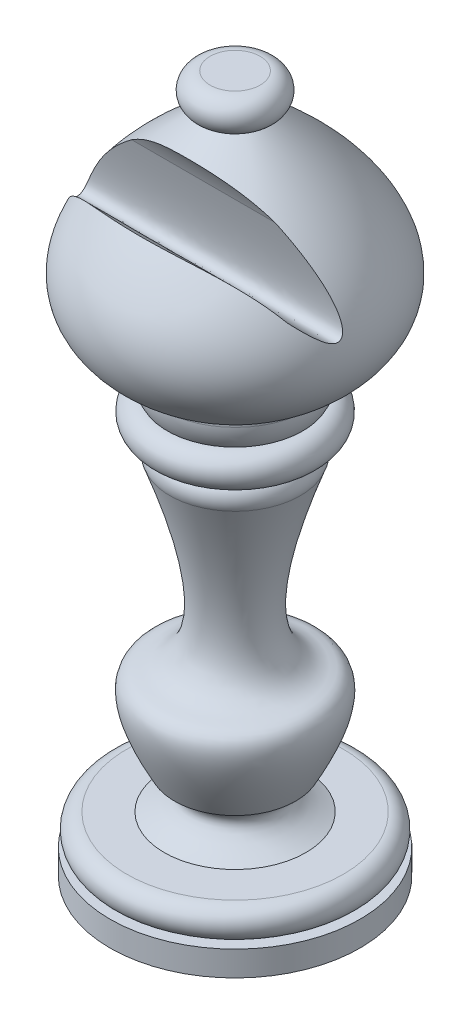
SolidWorks part; units mm, degrees
ref_plane "Front Plane" through (0, 0, 0) normal (0, 0, 1) x (1, 0, 0)
ref_plane "Top Plane" through (0, 0, 0) normal (0, 1, 0) x (1, 0, 0)
ref_plane "Right Plane" through (0, 0, 0) normal (1, 0, 0) x (0, 0, -1)
sketch "Sketch1" plane through (0, 0, 0) normal (0, 1, 0) x (1, 0, 0)
  line L1 (-16.1768, -16.5151) -> (16.1768, -16.5151) construction
  line L2 (-16.1768, -16.5151) -> (-16.1768, 16.5151) construction
  line L3 (-16.1768, 16.5151) -> (16.1768, 16.5151) construction
  line L4 (16.1768, -16.5151) -> (16.1768, 16.5151) construction
  line L5 (-16.1768, -16.5151) -> (16.1768, 16.5151) construction
  line L6 (-16.1768, 16.5151) -> (16.1768, -16.5151) construction
  circle A0 centre (0, 0) radius 15
  point P0 (0, 0)
  dimension "D1" = 30
extrude "Boss-Extrude1" add sketch "Sketch1" along normal blind 3
sketch "Sketch2" plane through (0, 0, 0) normal (0, 0, 1) x (1, 0, 0)
  line L0 (0, 0) -> (0, 11.4072) construction
  line L1 (15, 3) -> (-15, 3) construction
  line L2 (13, 3) -> (0, 3)
  line L3 (13, 6.6728) -> (8.4994, 6.6728)
  line L5 (7.2741, 11.4072) -> (0, 11.4072)
  line L6 (0, 3) -> (0, 11.4072)
  arc A0 (13, 3) -> (13, 6.6728) centre (13, 4.8364) ccw
  spline S0 degree 2 poles (8.4994, 6.6728) (2.7826, 9.1026) (7.2741, 11.4072) knots 0 0 0 1 1 1
  dimension "D1" = 2
revolve "Revolve1" add sketch "Sketch2" angle 360 about L0
sketch "Sketch3" plane through (0, 0, 0) normal (0, 0, 1) x (1, 0, 0)
  line L0 (0, 0) -> (0, 53.285) construction
  line L2 (7.2741, 11.4072) -> (-7.2741, 11.4072) construction
  line L3 (7.2741, 11.4072) -> (0, 11.4072)
  line L4 (6.0335, 46.296) -> (8.1263, 46.296)
  line L5 (8.1263, 50.296) -> (8.8239, 50.296)
  line L6 (8.8239, 50.296) -> (8.8239, 53.285)
  line L7 (8.8239, 53.285) -> (0, 53.285)
  line L8 (0, 11.4072) -> (0, 53.285)
  arc A0 (7.8298, 43.4168) -> (6.0335, 46.296) centre (6.0335, 44.296) ccw
  arc A1 (8.1263, 46.296) -> (8.1263, 50.296) centre (8.1263, 48.296) ccw
  spline S0 degree 2 poles (7.8298, 43.4168) (0.4858, 23.2013) (12.4322, 20.9438) (7.2741, 11.4072) knots 0 0 0 0.660085 1 1 1
  dimension "D1" = 2
revolve "Revolve2" add sketch "Sketch3" angle 360 about L0
sketch "Sketch4" plane through (0, 0, 0) normal (1, 0, 0) x (0, 0, -1)
  line L0 (0, 53.285) -> (0, 81.5387) construction
  line L1 (8.8239, 53.285) -> (-8.8239, 53.285) construction
  line L2 (0, 53.285) -> (8.8239, 53.285)
  line L3 (0, 53.285) -> (0, 81.5387)
  spline S0 degree 2 poles (0, 81.5387) (26.7597, 63.2839) (8.8239, 53.285) knots 0 0 0 1 1 1
revolve "Revolve3" add sketch "Sketch4" angle 360 about L3
sketch "Sketch5" plane through (0, 0, 0) normal (1, 0, 0) x (0, 0, -1)
  line L0 (-19.9005, 74.7415) -> (-13.287, 82.3198)
  spline S0 degree 2 poles (-19.9005, 74.7415) (-11.6755, 74.63) (-6.805, 67.3863) knots 0 0 0 1 1 1
  spline S1 degree 2 poles (-6.805, 67.3863) (0.2222, 59.7056) (-3.8076, 74.0978) knots 0 0 0 1 1 1
  spline S2 degree 2 poles (-13.287, 82.3198) (-6.4144, 80.3398) (-3.8076, 74.0978) knots 0 0 0 1 1 1
extrude "Cut-Extrude1" cut sketch "Sketch5" against normal through all both and the other way through all
fillet "Fillet1" radius 5 1 edges at (0, 50.296, -8.8239)
sketch "Sketch6" plane through (0, 0, 0) normal (0, 0, 1) x (1, 0, 0)
  line L0 (0, 0) -> (0, 83.6703) construction
  line L1 (0, 79.6703) -> (3, 79.6703)
  line L2 (3, 83.6703) -> (0, 83.6703)
  line L3 (0, 83.6703) -> (0, 79.6703)
  arc A0 (3, 79.6703) -> (3, 83.6703) centre (3, 81.6703) ccw
  dimension "D1" = 2
  dimension "D2" = 3
revolve "Revolve4" add sketch "Sketch6" angle 360 about L0
